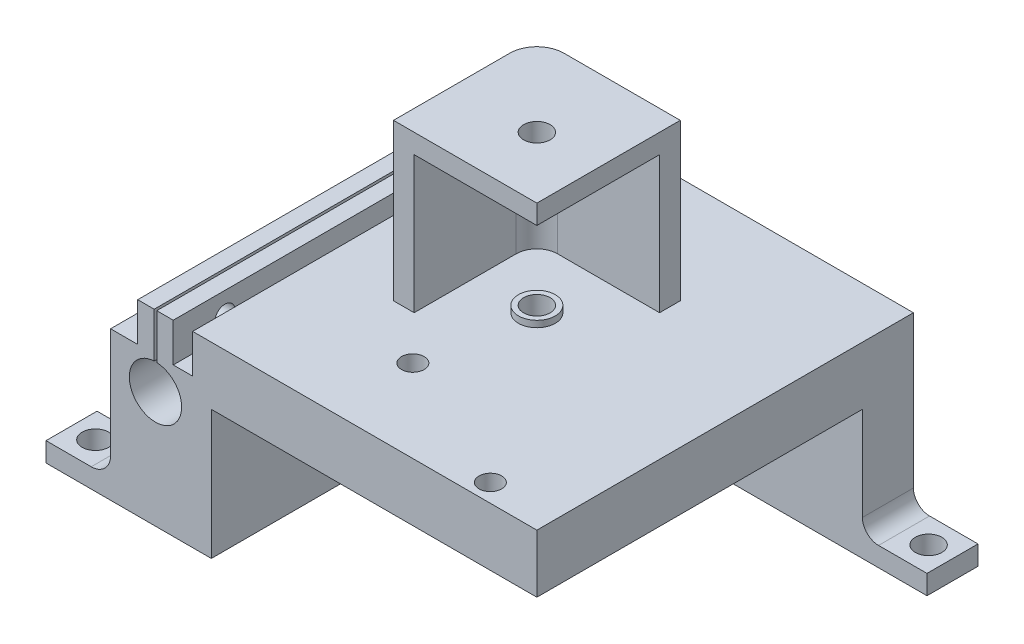
SolidWorks part; units mm, degrees
ref_plane "Спереди" through (0, 0, 0) normal (0, 0, 1) x (1, 0, 0)
ref_plane "Сверху" through (0, 0, 0) normal (0, 1, 0) x (1, 0, 0)
ref_plane "Справа" through (0, 0, 0) normal (1, 0, 0) x (0, 0, -1)
other "Configuration Table"
sketch "Sketch1" plane through (0, 0, 0) normal (0, 1, 0) x (1, 0, 0)
  line L0 (-33, 29.15) -> (-3.85, 29.15) construction
  line L1 (-33, -29.15) -> (33, -29.15)
  line L2 (-33, -29.15) -> (-33, 29.15)
  line L3 (-33, 29.15) -> (33, 29.15)
  line L4 (33, -29.15) -> (33, 29.15)
  line L5 (-33, -29.15) -> (33, 29.15) construction
  line L6 (-33, 29.15) -> (33, -29.15) construction
  line L7 (-3.85, 29.15) -> (-3.85, 0) construction
  circle A1 centre (-3.85, 0) radius 2.05
  point P0 (0, 0)
  dimension "D5" = 4.1
  dimension "D1" = 66
  dimension "D2" = 58.3
  dimension "D3" = 29.15
  dimension "D4" = 29.15
extrude "Boss-Extrude1" add sketch "Sketch1" along normal blind 29
sketch "Sketch3" plane through (0, 29, 0) normal (0, 1, 0) x (1, 0, 0)
  line L0 (-33, 21.25) -> (-33, -21.25)
  line L1 (-33, 29.15) -> (-33, -29.15) construction
  line L2 (-33, -21.25) -> (17.4, -21.25)
  line L4 (-33, -29.15) -> (33, -29.15) construction
  line L6 (17.4, -21.25) -> (17.4, 21.25)
  line L7 (33, 29.15) -> (-33, 29.15) construction
  line L10 (-25.1, 21.25) -> (-33, 21.25)
  line L11 (-25.1, 21.25) -> (17.4, 21.25)
  dimension "D1" = 7.9
  dimension "D2" = 50.4
  dimension "D3" = 7.9
extrude "Cut-Extrude1" cut sketch "Sketch3" along normal blind 20 from surface starting at face at (0, 0, 0)
sketch "Sketch6" plane through (0, 0, 0) normal (0, -1, 0) x (1, 0, 0)
  line L0 (-33, 29.15) -> (-33, 21.25)
  line L1 (-33, 29.15) -> (-43, 29.15)
  line L2 (-33, 21.25) -> (-43, 21.25)
  line L3 (-43, 29.15) -> (-43, 21.25)
  line L4 (-33, -21.25) -> (-33, -29.15)
  line L5 (-33, -21.25) -> (-43, -21.25)
  line L6 (-33, -29.15) -> (-43, -29.15)
  line L7 (-43, -21.25) -> (-43, -29.15)
  line L8 (33, 29.15) -> (33, 21.25)
  line L9 (33, 29.15) -> (43, 29.15)
  line L10 (33, 21.25) -> (43, 21.25)
  line L11 (43, 29.15) -> (43, 21.25)
  line L12 (33, 29.15) -> (33, -29.15) construction
  line L13 (33, -21.25) -> (33, -29.15)
  line L14 (33, -21.25) -> (43, -21.25)
  line L15 (33, -29.15) -> (43, -29.15)
  line L16 (43, -21.25) -> (43, -29.15)
  line L17 (-38, -21.25) -> (-38, -29.15) construction
  line L18 (-38, 29.15) -> (-38, 21.25) construction
  line L19 (38, 29.15) -> (38, 21.25) construction
  line L20 (38, -21.25) -> (38, -29.15) construction
  circle A0 centre (-39.3, -25.2) radius 2.05
  circle A1 centre (-39.3, 25.2) radius 2.05
  circle A2 centre (39.3, 25.2) radius 2.05
  circle A3 centre (39.3, -25.2) radius 2.05
  dimension "D9" = 4.1
  dimension "D10" = 3.7
  dimension "D1" = 10
  dimension "D2" = 7.9
  dimension "D3" = 10
  dimension "D4" = 10
  dimension "D5" = 10
  dimension "D6" = 7.9
  dimension "D7" = 7.9
  dimension "D8" = 7.9
  dimension "D11" = 3.7
  dimension "D12" = 3.7
  dimension "D13" = 3.7
  dimension "D14" = 3.7
extrude "Boss-Extrude2" add sketch "Sketch6" against normal blind 3
sketch "Sketch7" plane through (0, 0, -29.15) normal (0, 0, -1) x (-1, 0, 0)
  line L0 (-33, 7) -> (-33, 6)
  line L1 (-33, 29) -> (-33, 3) construction
  line L2 (-36, 3) -> (-37, 3)
  line L3 (-33, 3) -> (-43, 3) construction
  line L4 (33, 7) -> (33, 5.5)
  line L5 (33, 29) -> (33, 3) construction
  line L6 (43, 3) -> (33, 3) construction
  line L7 (35.5, 3) -> (37, 3)
  line L8 (-36, 3) -> (-33, 3)
  line L9 (-33, 3) -> (-33, 6)
  line L10 (-36, 3) -> (-33, 3)
  line L11 (-33, 3) -> (-33, 6)
  line L12 (-36, 3) -> (-36, 2.3913)
  line L13 (33, 5.5) -> (33, 3)
  line L14 (33, 3) -> (35.5, 3)
  arc A0 (-33, 6) -> (-36, 3) centre (-36, 6) cw
  arc A1 (35.5, 3) -> (33, 5.5) centre (35.5, 5.5) cw
  point P10 (-33, 3)
  point P20 (33, 3)
  line M8 (43, 3) -> (33, 3)
  line M9 (33, 3) -> (33, 29)
  line M11 (-33, 29) -> (-33, 3)
  line M12 (-33, 3) -> (-43, 3)
  dimension "D3" = 3
  dimension "D6" = 2.5
  dimension "D1" = 4
  dimension "D2" = 4
  dimension "D4" = 4
  dimension "D5" = 4
extrude "Boss-Extrude4" add sketch "Sketch7" against normal up to surface (7.9 mm away) contours A1 M8 M9 | A0 M11 M12 region at (33.6701, 3.6701, -29.15) region at (-33.5584, 3.5584, -29.15) up to face at (38, 1.5, -21.25)
extrude "Boss-Extrude5" add sketch "Sketch7<5>" along normal up to surface (-50.4 mm away) from surface contours A1 M8 M9 | A0 M11 M12 region at (33.6701, 3.6701, -29.15) region at (-33.5584, 3.5584, -29.15) up to face at (-19.5333, 7.6667, 21.25) starting at face at (0, 8.75, 29.15)
sketch "Sketch7<5>" plane through (0, 0, -29.15) normal (0, 0, -1) x (-1, 0, 0) same geometry as "Sketch7"
sketch "Sketch8" plane through (0, 0, 29.15) normal (0, 0, 1) x (1, 0, 0)
  line L0 (17.4, 0) -> (26.05, 0) construction
  line L1 (-43, 0) -> (43, 0) construction
  line L2 (26.05, 0) -> (26.05, 18) construction
  line L3 (33, 29) -> (33, 6) construction
  circle A0 centre (26.05, 18) radius 4.05
  dimension "D3" = 8.1
  dimension "D1" = 6.95
  dimension "D2" = 18
extrude "Cut-Extrude4" cut sketch "Sketch8" along normal up to next from surface starting at face at (0.0396, 8.0361, -29.15)
sketch "Sketch10" plane through (0, 0, -29.15) normal (0, 0, -1) x (-1, 0, 0)
  line L0 (-33, 29) -> (-28.8, 29) construction
  line L1 (-33, 29) -> (33, 29) construction
  line L2 (-28.8, 29) -> (-23.3, 29) construction
  line L3 (-26.05, 18) -> (-22, 18) construction
  line L4 (-17.4, 20) -> (-17.4, 0) construction
  line L5 (-23.3, 23) -> (-23.3, 25.6) construction
  line L6 (-23.3, 29) -> (-20.3, 29)
  line L7 (-23.3, 29) -> (-23.3, 23)
  line L8 (-23.3, 23) -> (-20.3, 23)
  line L9 (-20.3, 29) -> (-20.3, 23)
  line L10 (-33, 29) -> (-33, 6) construction
  line L11 (-28.8, 29) -> (-33, 29)
  line L12 (-28.8, 29) -> (-28.8, 23)
  line L13 (-28.8, 23) -> (-33, 23)
  line L14 (-33, 29) -> (-33, 23)
  line L15 (-23.3, 23) -> (-23.3, 28.2) construction
  line L16 (-23.3, 23) -> (-23.3, 25.6) construction
  line L17 (-23.3, 25.6) -> (-28.8, 25.6) construction
  line L19 (-26.05, 29) -> (-26.05, 23) construction
  line L20 (-26.05, 18) -> (-26.05, 29) construction
  line L21 (-26.25, 29) -> (-25.85, 29)
  line L22 (-26.25, 29) -> (-26.25, 21.3825)
  line L23 (-26.25, 21.3825) -> (-25.85, 21.3825)
  line L24 (-25.85, 29) -> (-25.85, 21.3825)
  circle A0 centre (-26.05, 18) radius 4.05 construction
  dimension "D8" = 0.2
  dimension "D1" = 9.7
  dimension "D2" = 3
  dimension "D3" = 5.5
  dimension "D4" = 6
  dimension "D5" = 2.9
  dimension "D6" = 2.6
  dimension "D7" = 4.2
  dimension "D9" = 0.2
  dimension "D10" = 2.55
  dimension "D11" = 2.55
extrude "Cut-Extrude5" cut sketch "Sketch10" against normal up to next
sketch "Sketch11" plane through (28.8, 0, 0) normal (1, 0, 0) x (0, 0, -1)
  line L0 (-29.15, 23) -> (-21.15, 23) construction
  line L1 (-29.15, 23) -> (29.15, 23) construction
  line L2 (-21.15, 23) -> (-21.15, 25.6) construction
  line L3 (0, 29) -> (0, 23) construction
  line L4 (-29.15, 29) -> (29.15, 29) construction
  circle A0 centre (-21.15, 25.6) radius 1.55
  circle A1 centre (21.15, 25.6) radius 1.55
  dimension "D3" = 3.1
  dimension "D1" = 8
  dimension "D2" = 2.6
extrude "Cut-Extrude6" cut sketch "Sketch11" against normal up to surface (5.5 mm away) up to face at (23.3, 26, 0)
sketch "Sketch12" plane through (0, 20, 0) normal (0, -1, 0) x (1, 0, 0)
  line L1 (-7.95, 0) -> (-5.9, -3.5507)
  line L2 (-5.9, -3.5507) -> (-1.8, -3.5507)
  line L3 (-1.8, -3.5507) -> (0.25, 0)
  line L4 (0.25, 0) -> (-1.8, 3.5507)
  line L5 (-1.8, 3.5507) -> (-5.9, 3.5507)
  line L6 (-5.9, 3.5507) -> (-7.95, 0)
  circle A0 centre (-3.85, 0) radius 3.5507 construction
  dimension "D1" = 8.2
extrude "Cut-Extrude7" cut sketch "Sketch12" against normal blind 2.5
sketch "Sketch13" plane through (0, 29, 0) normal (0, 1, 0) x (1, 0, 0)
  line L0 (-3.85, 0) -> (-3.85, 9.5) construction
  line L1 (-3.85, 0) -> (5.65, 0) construction
  line L2 (-3.85, 9.5) -> (-13.35, 9.5) construction
  line L3 (5.65, 0) -> (5.65, -9.5) construction
  line L4 (-13.35, 9.5) -> (-13.35, 12.7)
  line L5 (-13.35, 12.7) -> (4.65, 12.7)
  line L6 (8.85, 8.5) -> (8.85, -9.5)
  line L7 (8.85, -9.5) -> (5.65, -9.5)
  line L8 (5.65, -9.5) -> (5.65, 6.3)
  line L9 (2.45, 9.5) -> (-13.35, 9.5)
  arc A0 (5.65, 6.3) -> (2.45, 9.5) centre (2.45, 6.3) ccw
  arc A1 (8.85, 8.5) -> (4.65, 12.7) centre (4.65, 8.5) ccw
  point P15 (8.85, 12.7)
  dimension "D1" = 3.2
  dimension "D6" = 3.2
  dimension "D7" = 4.2
  dimension "D2" = 9.5
  dimension "D3" = 3.2
  dimension "D4" = 22.2
  dimension "D5" = 22.2
extrude "Boss-Extrude6" add sketch "Sketch13" along normal blind 21.2
sketch "Sketch14" plane through (0, 50.2, 0) normal (0, 1, 0) x (1, 0, 0)
  line L1 (-13.35, 12.7) -> (4.65, 12.7)
  line L2 (-13.35, 12.7) -> (-13.35, -9.5)
  line L3 (-13.35, -9.5) -> (8.85, -9.5)
  line L4 (8.85, 8.5) -> (8.85, -9.5)
  circle A0 centre (-3.85, 0) radius 2.05
  arc A1 (8.85, 8.5) -> (4.65, 12.7) centre (4.65, 8.5) ccw
  dimension "D1" = 4.1
  dimension "D2" = 4.2
extrude "Boss-Extrude7" add sketch "Sketch14" along normal blind 3
sketch "Sketch15" plane through (0, 53.2, 0) normal (0, 1, 0) x (1, 0, 0)
  circle A0 centre (-3.85, 0) radius 2.85
  circle A1 centre (-3.85, 0) radius 2.05
  dimension "D1" = 4.1
  dimension "D2" = 0.8
extrude "Boss-Extrude8" add sketch "Sketch15" against normal blind 1 from surface starting at face at (-3.85, 50.2, 2.05)
extrude "Boss-Extrude9" add sketch "Sketch15<2>" along normal blind 1 from surface starting at face at (-6.35, 29, 0)
sketch "Sketch15<2>" plane through (0, 53.2, 0) normal (0, 1, 0) x (1, 0, 0) same geometry as "Sketch15"
mirror "Mirror2" about plane through (-43, 3, -21.25) normal (-1, 0, 0) of bodies 118
delete or keep bodies "Body-Delete/Keep 1" type delete bodies bodies 118
sketch "Sketch16" plane through (0, 0, 0) normal (0, -1, 0) x (1, 0, 0)
  line L0 (-43, 29.15) -> (-129, 29.15) construction
  line L1 (-103.4, 21.25) -> (-42.9481, 21.25)
  line L2 (-103.4, 21.25) -> (-103.4, 29.15)
  line L3 (-103.4, 29.15) -> (-42.9481, 29.15)
  line L4 (-42.9481, 21.25) -> (-42.9481, 29.15)
extrude "Cut-Extrude8" cut sketch "Sketch16" against normal up to surface (20 mm away) up to face at (-82.15, 20, 0)
sketch "Sketch19" plane through (0, 20, 0) normal (0, -1, 0) x (1, 0, 0)
  line L0 (-53, 29.15) -> (-63, 29.15) construction
  line L1 (-103.4, 29.15) -> (-53, 29.15) construction
  line L2 (-63, 29.15) -> (-63, 26.35) construction
  line L3 (-63, 26.35) -> (-85, 26.35) construction
  line L4 (-85, 26.35) -> (-85, 16.35) construction
  circle A0 centre (-85, 16.35) radius 1.75
  circle A1 centre (-63, 26.35) radius 1.75
  dimension "D5" = 3.5
  dimension "D1" = 2.8
  dimension "D2" = 22
  dimension "D3" = 10
  dimension "D4" = 10
extrude "Cut-Extrude9" cut sketch "Sketch19" against normal up to surface (9 mm away) from surface up to face at (-82.15, 29, -2.85) starting at face at (-82.15, 20, 0)
